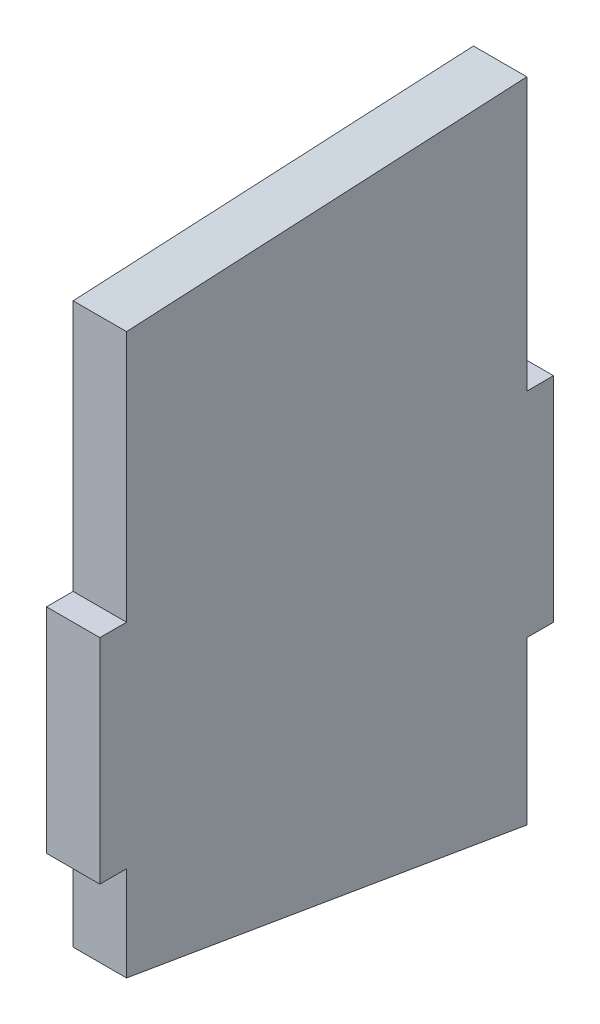
SolidWorks part; units mm, degrees
material "Pink Foam"
ref_plane "Front Plane" through (0, 0, 0) normal (0, 0, 1) x (1, 0, 0)
ref_plane "Top Plane" through (0, 0, 0) normal (0, 1, 0) x (1, 0, 0)
ref_plane "Right Plane" through (0, 0, 0) normal (1, 0, 0) x (0, 0, -1)
sketch "Sketch1" plane through (0, 0, 0) normal (1, 0, 0) x (0, 0, -1)
  line L0 (-95.25, 170.5633) -> (95.25, 180.3237)
  line L1 (-95.25, -203.2) -> (95.25, -203.2)
  line L2 (-95.25, -203.2) -> (-95.25, 203.2)
  line L3 (-95.25, 203.2) -> (95.25, 203.2)
  line L4 (95.25, -203.2) -> (95.25, 203.2)
  line L5 (-95.25, -203.2) -> (95.25, 203.2) construction
  line L6 (-95.25, 203.2) -> (95.25, -203.2) construction
  line L7 (-107.95, -50.8) -> (107.95, -50.8)
  line L8 (-107.95, -50.8) -> (-107.95, 50.8)
  line L9 (-107.95, 50.8) -> (107.95, 50.8)
  line L10 (107.95, -50.8) -> (107.95, 50.8)
  line L11 (-107.95, -50.8) -> (107.95, 50.8) construction
  line L12 (-107.95, 50.8) -> (107.95, -50.8) construction
  line L14 (-95.25, -95.8238) -> (95.25, -128.0296)
  point P0 (0, 0)
  point P6 (0, 0)
  dimension "D1" = 190.5
  dimension "D2" = 215.9
  dimension "D3" = 101.6
  dimension "D4" = 406.4
  dimension "D5" = 32.6367
  dimension "D6" = 22.8763
  dimension "D7" = 75.1704
  dimension "D8" = 266.3871
extrude "Boss-Extrude1" add sketch "Sketch1" along normal blind 25.4 contours L2 L9 L4 L0 | L7 L10 L9 L4 | L9 L2 L7 L4 | L9 L8 L7 L2 | L2 L14 L4 L7 region at (0, 113.1536, -1.2431) region at (0, 0, 0) region at (0, 0, 101.6) region at (0, 0, -101.6) region at (0, -82.0704, -8.364)
